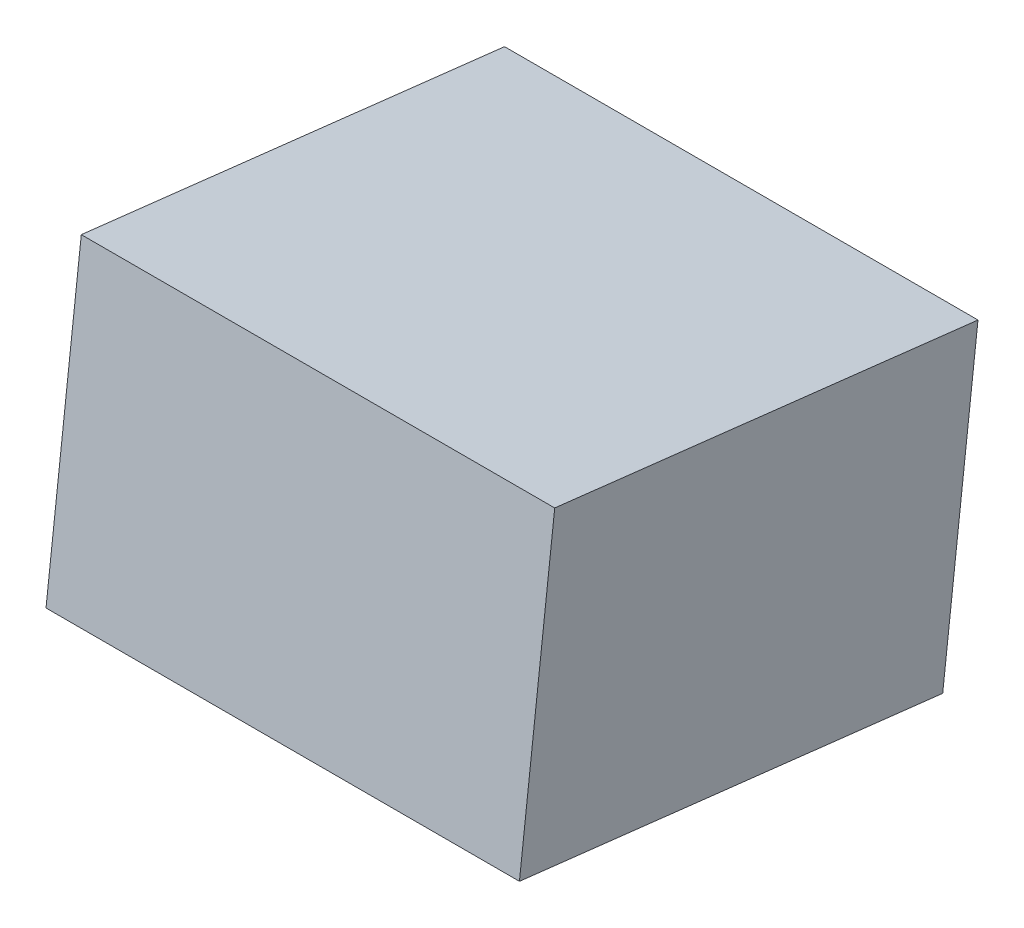
SolidWorks part; units mm, degrees
ref_plane "Front Plane" through (0, 0, 0) normal (0, 0, 1) x (1, 0, 0)
ref_plane "Top Plane" through (0, 0, 0) normal (0, 1, 0) x (1, 0, 0)
ref_plane "Right Plane" through (0, 0, 0) normal (1, 0, 0) x (0, 0, -1)
sketch "Sketch1" plane through (0, 358.8799, -41.4225) normal (0, 0.9934, -0.1147) x (1, 0, 0)
  line L1 (-235, 75.2443) -> (-35, 75.2443)
  line L2 (-235, 75.2443) -> (-235, 255.2443)
  line L3 (-235, 255.2443) -> (-35, 255.2443)
  line L4 (-35, 75.2443) -> (-35, 255.2443)
  line L5 (-235, 75.2443) -> (-35, 255.2443) construction
  line L6 (-235, 255.2443) -> (-35, 75.2443) construction
  point P0 (-135, 165.2443)
  dimension "D1" = 180
  dimension "D2" = 200
extrude "Boss-Extrude1" add sketch "Sketch1" along normal blind 130
